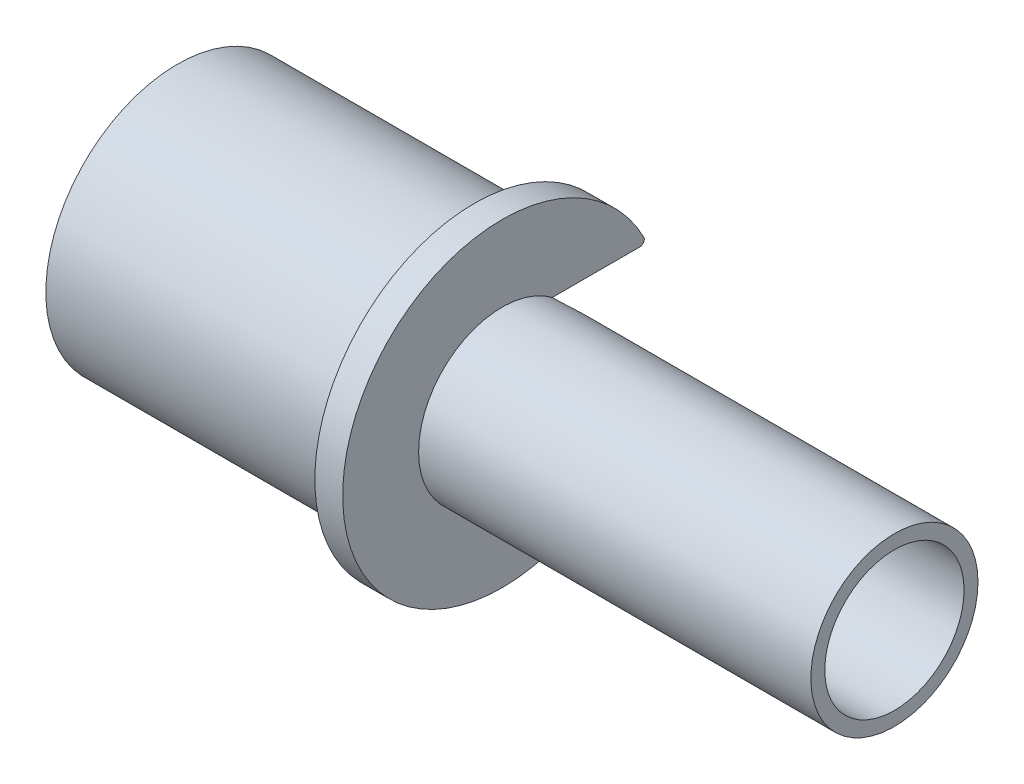
SolidWorks part; units mm, degrees
material "6061-T6 (SS)"
ref_plane "Front Plane" through (0, 0, 0) normal (0, 0, 1) x (1, 0, 0)
ref_plane "Top Plane" through (0, 0, 0) normal (0, 1, 0) x (1, 0, 0)
ref_plane "Right Plane" through (0, 0, 0) normal (1, 0, 0) x (0, 0, -1)
sketch "Sketch1" plane through (0, 0, 0) normal (0, 0, 1) x (1, 0, 0)
  line L0 (0, 0) -> (-16.6687, 0) construction
  line L1 (-1.4625, 3.9687) -> (-1.4625, 4.7625)
  line L2 (-1.4625, 4.7625) -> (-23.8125, 4.7625)
  line L3 (-23.8125, 4.7625) -> (-23.8125, 9.0875)
  line L4 (-23.8125, 9.0875) -> (-25.4, 9.0875)
  line L5 (-25.4, 9.0875) -> (-25.4, 7.5)
  line L6 (-25.4, 7.5) -> (-42.315, 7.5)
  line L7 (-42.315, 7.5) -> (-42.315, 3.9687)
  line L8 (-42.315, 3.9687) -> (-1.4625, 3.9687)
  line L9 (-25.4, -15.27) -> (-25.4, 15.27) construction
  line L10 (-50.8, -5.5563) -> (-50.8, 5.5563) construction
  line L14 (-1.4625, -11.375) -> (-1.4625, 11.375) construction
  dimension "D1" = 7.9375
  dimension "D4" = 15
  dimension "D3" = 9.525
  dimension "D2" = 1.5875
  dimension "D5" = 1.5875
  dimension "D6" = 8.485
revolve "Revolve1" add sketch "Sketch1" angle 360 about L0
sketch "Sketch2" plane through (-1.4625, 0, 0) normal (1, 0, 0) x (0, 0, -1)
  line L0 (1.3441, 3.7342) -> (8.2848, 3.7342)
  line L1 (8.2848, -3.7342) -> (1.3441, -3.7342)
  line L2 (0, 0) -> (14.3216, 0) construction
  circle A0 centre (0, 0) radius 3.9687 construction
  circle A1 centre (0, 0) radius 9.0875 construction
  arc A2 (1.3441, 3.7342) -> (1.3441, -3.7342) centre (0, 0) cw
  arc A3 (8.2848, 3.7342) -> (8.2848, -3.7342) centre (0, 0) cw
  arc A4 (3.6742, 3.7342) -> (3.6742, -3.7342) centre (0, 0) cw construction
  circle A5 centre (5.2387, 0) radius 1.27 construction
  circle A6 centre (4.623, 2.4642) radius 1.27 construction
  circle A7 centre (4.623, -2.4642) radius 1.27 construction
  dimension "D1" = 1.27
  dimension "D2" = 2.54
extrude "Cut-Extrude1" [suppressed] cut sketch "Sketch2" against normal through all both
sketch "Sketch3" plane through (0, 0, 0) normal (0, 0, 1) x (1, 0, 0)
  line L0 (-42.315, 3.81) -> (-42.315, -3.81)
  line L1 (-42.315, 7.5) -> (-42.315, -7.5) construction
  line L2 (-42.315, -3.81) -> (-23.8125, -3.81)
  line L4 (-23.8125, 3.81) -> (-42.315, 3.81)
  line L5 (-20.6375, -0.635) -> (-20.6375, 0.635)
  line L6 (-20.6375, 0) -> (0, 0) construction
  line L8 (-23.8125, -9.0875) -> (-23.8125, 9.0875) construction
  arc A1 (-23.8125, -3.81) -> (-20.6375, -0.635) centre (-23.8125, -0.635) ccw
  arc A2 (-20.6375, 0.635) -> (-23.8125, 3.81) centre (-23.8125, 0.635) ccw
  dimension "D1" = 7.62
  dimension "D2" = 3.175
extrude "Cut-Extrude2" cut sketch "Sketch3" against normal up to next
fillet "Fillet1" radius 0.254 4 edges at (-24.6062, 3.81, -8.2502) (-24.6062, -3.81, -8.2502) (-33.8575, -3.81, -6.4602) (-33.8575, 3.81, -6.4602)
equation "\"bearing1\"=0.273438"
equation "\"D1@Sketch1\"=5/16"
equation "\"D4@Sketch1\"=15mm"
equation "\"D6@Sketch1\"=.275+1.5mm"
